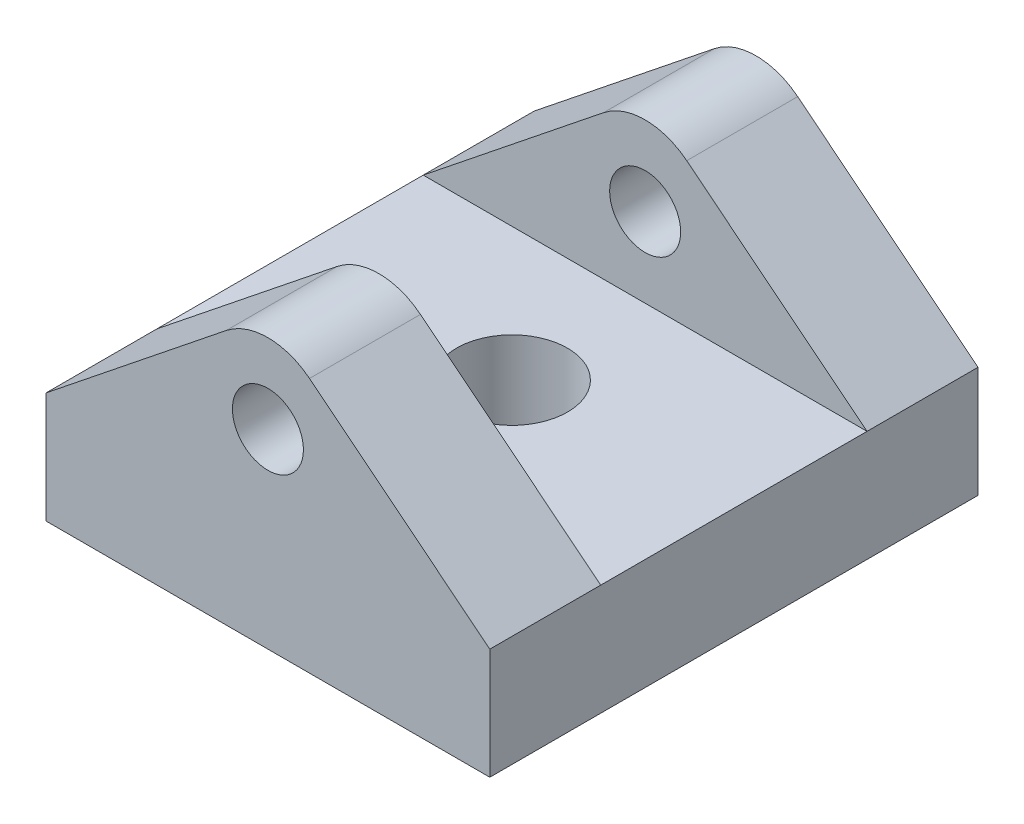
SolidWorks part; units mm, degrees
ref_plane "Front Plane" through (0, 0, 0) normal (0, 0, 1) x (1, 0, 0)
ref_plane "Top Plane" through (0, 0, 0) normal (0, 1, 0) x (1, 0, 0)
ref_plane "Right Plane" through (0, 0, 0) normal (1, 0, 0) x (0, 0, -1)
sketch "Sketch1" plane through (0, 0, 0) normal (0, 1, 0) x (1, 0, 0)
  line L0 (-10, 6) -> (10, 6)
  line L1 (-10, 11) -> (10, 11)
  line L2 (-10, 11) -> (-10, -11)
  line L3 (-10, -11) -> (10, -11)
  line L4 (10, 11) -> (10, -11)
  line L5 (-10, 11) -> (10, -11) construction
  line L6 (-10, -11) -> (10, 11) construction
  line L7 (-10, -6) -> (10, -6)
  point P0 (0, 0)
  dimension "D1" = 20
  dimension "D2" = 22
  dimension "D3" = 5
  dimension "D4" = 5
extrude "Boss-Extrude1" add sketch "Sketch1" along normal blind 5 contours L4 L1 L2 L0 | L2 L7 L4 L0 | L7 L2 L3 L4 region at (0, 0, -8.5) region at (0, 0, 0) region at (0, 0, 8.5)
sketch "Sketch2" plane through (0, 0, 11) normal (0, 0, 1) x (1, 0, 0)
  line L0 (-10, 5) -> (0, 13)
  line L1 (0, 13) -> (10, 5)
  line L2 (10, 5) -> (-10, 5)
  point P6 (0, 5)
  dimension "D1" = 8
extrude "Boss-Extrude2" add sketch "Sketch2" along direction (0, 0, 1) on the side against the normal blind 5
extrude "Boss-Extrude3" add sketch "Sketch2<2>" along normal blind 5 from surface starting at face at (0, 2.5, -11)
sketch "Sketch2<2>" plane through (0, 0, 11) normal (0, 0, 1) x (1, 0, 0) same geometry as "Sketch2"
fillet "Fillet1" radius 3 2 edges at (0, 13, -8.5) (0, 13, 8.5)
hole_wizard "Ø5.0 (5) Diameter Hole1" positions "Sketch3" profile "Sketch4" hole size "Ø5.0" standard "ANSI Metric" end condition up to next
sketch "Sketch3" plane through (0, 5, 0) normal (0, 1, 0) x (1, 0, 0)
  point P0 (0, 0)
sketch "Sketch4" plane through (0, 5, 0) normal (1, 0, 0) x (0, 0, 1)
  line L0 (0, 0) -> (0, 5)
  line L1 (0, 5) -> (2.5, 5)
  line L2 (2.5, 5) -> (2.5, 0)
  line L5 (2.5, 0) -> (0, 0)
  line L11 (0, -6.35) -> (0, 107.95) construction
  dimension "Thru Hole Dia." = 5
  dimension "Thru Hole Depth" = 5
hole_wizard "Ø2.4 M2 clearance <1>" positions "Sketch5" profile "Sketch6" hole size "Ø3.2" standard "ANSI Metric" end condition up to next
sketch "Sketch5" plane through (0, 0, -11) normal (0, 0, 1) x (1, 0, 0)
  line L0 (0, 12.1581) -> (0, 5) construction
  line L1 (10, 5) -> (-10, 5) construction
  arc A0 (1.8741, 11.5007) -> (-1.8741, 11.5007) centre (0, 9.1581) ccw construction
  point P0 (0, 8.5791)
sketch "Sketch6" plane through (0, 8.5791, -11) normal (1, 0, 0) x (0, 1, 0)
  line L0 (0, 0) -> (0, 5)
  line L1 (0, 5) -> (1.6, 5)
  line L2 (1.6, 5) -> (1.6, 0)
  line L5 (1.6, 0) -> (0, 0)
  line L11 (0, -6.35) -> (0, 107.95) construction
  dimension "Thru Hole Dia." = 3.2
  dimension "Thru Hole Depth" = 5
sketch "Sketch7" plane through (0, 0, 11) normal (0, 0, 1) x (1, 0, 0)
  point P0 (0, 8.5791)
hole_wizard "Ø3.2 (3.2) M2 heatset" positions "Sketch7" profile "Sketch8" hole size "Ø3.2" standard "ANSI Metric" end condition up to next
sketch "Sketch8" plane through (0, 8.5791, 11) normal (1, 0, 0) x (0, -1, 0)
  line L0 (0, 0) -> (0, 5)
  line L1 (0, 5) -> (1.6, 5)
  line L2 (1.6, 5) -> (1.6, 0)
  line L5 (1.6, 0) -> (0, 0)
  line L11 (0, -6.35) -> (0, 107.95) construction
  dimension "Thru Hole Dia." = 3.2
  dimension "Thru Hole Depth" = 5
